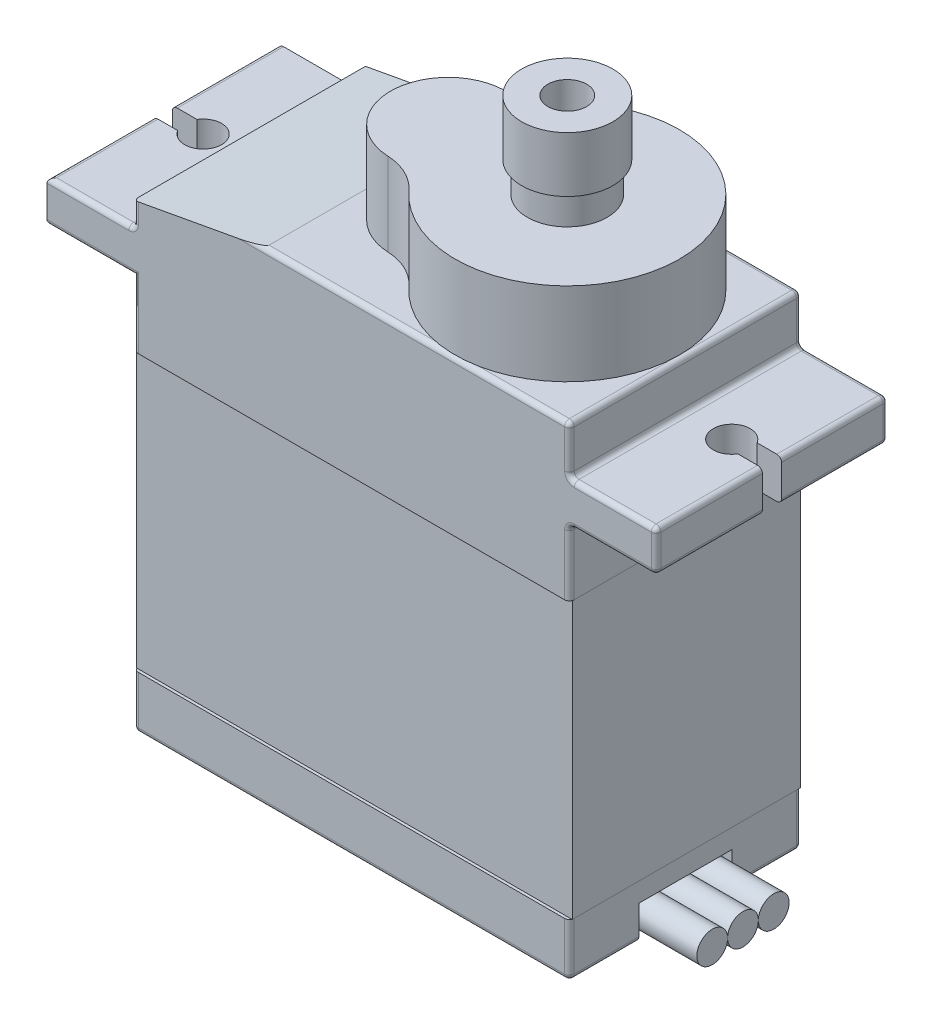
SolidWorks part; units mm, degrees
note: '?' marks a value the reader was unsure of.
ref_plane "Alzado" through (0, 0, 0) normal (0, 0, 1) x (1, 0, 0)
ref_plane "Planta" through (0, 0, 0) normal (0, 1, 0) x (1, 0, 0)
ref_plane "Vista lateral" through (0, 0, 0) normal (1, 0, 0) x (0, 0, -1)
sketch "Croquis1" plane through (0, 0, 0) normal (0, 1, 0) x (1, 0, 0)
  line L1 (-11.335, 6.03) -> (11.335, 6.03)
  line L2 (-11.335, 6.03) -> (-11.335, -6.03)
  line L3 (-11.335, -6.03) -> (11.335, -6.03)
  line L4 (11.335, 6.03) -> (11.335, -6.03)
  line L5 (-11.335, 6.03) -> (11.335, -6.03) construction
  line L6 (-11.335, -6.03) -> (11.335, 6.03) construction
  point P0 (0, 0)
  dimension "D1" = 22.67
  dimension "D2" = 12.06
extrude "Saliente-Extruir1" add sketch "Croquis1" along normal blind 25.15
sketch "Croquis2" plane through (11.335, 0, 0) normal (1, 0, 0) x (0, 0, -1)
  line L0 (-6.03, 0) -> (-6.03, 20.53) construction
  line L1 (-6.03, 25.15) -> (-6.03, 0) construction
  line L2 (-6.03, 20.53) -> (6.03, 20.53)
  line L3 (6.03, 25.15) -> (6.03, 0) construction
  line L4 (-6.03, 22.66) -> (6.03, 22.66)
  line L5 (-6.03, 22.66) -> (-6.03, 20.53)
  line L6 (6.03, 22.66) -> (6.03, 20.53)
  dimension "D1" = 20.53
  dimension "D2" = 2.13
extrude "Saliente-Extruir2" add sketch "Croquis2" along normal blind 4.51
sketch "Croquis5" plane through (-11.335, 0, 0) normal (-1, 0, 0) x (0, 0, 1)
  line L1 (6.03, 25.15) -> (6.03, 0) construction
  line L2 (-6.03, 22.66) -> (6.03, 22.66)
  line L3 (-6.03, 22.66) -> (-6.03, 20.53)
  line L4 (-6.03, 20.53) -> (6.03, 20.53)
  line L5 (6.03, 22.66) -> (6.03, 20.53)
  line L8 (-6.03, 0) -> (6.03, 0) construction
  dimension "D1" = 20.53
extrude "Saliente-Extruir3" add sketch "Croquis5" along normal blind 4.51
fillet "Redondeo1" radius 0.25 30 edges at (11.335, 0, 0) (0, 0, -6.03) (0, 0, 6.03) (-11.335, 0, 0) (0, 25.15, -6.03) (0, 25.15, 6.03) (-11.335, 25.15, 0) (11.335, 25.15, 0) (15.845, 21.595, -6.03) (15.845, 21.595, 6.03) (15.845, 20.53, 0) (15.845, 22.66, 0) (-15.845, 20.53, 0) (-15.845, 22.66, 0)
sketch "Croquis6" plane through (0, 22.66, 0) normal (0, 1, 0) x (1, 0, 0)
  line L0 (-15.595, 6.03) -> (-11.585, -5.78) construction
  line L1 (-11.585, -5.78) -> (-11.585, 6.03) construction
  line L2 (-11.585, 6.03) -> (-15.595, -5.78) construction
  line L3 (0, 0) -> (0, 5.78) construction
  line L4 (11.085, 5.78) -> (-11.085, 5.78) construction
  line L5 (0, 5.78) -> (0, -5.78) construction
  line L6 (-11.085, -5.78) -> (11.085, -5.78) construction
  line L7 (-22.4686, 0) -> (24.1195, 0) construction
  line L9 (-14.5695, 0.5) -> (-16.5695, 0.5)
  line L10 (-14.5695, -0.5) -> (-16.5695, -0.5)
  line L11 (-16.5695, -0.5) -> (-16.5695, 0.5)
  line L12 (14.5695, 0.5) -> (16.5695, 0.5)
  line L13 (16.5695, -0.5) -> (16.5695, 0.5)
  line L14 (14.5695, -0.5) -> (16.5695, -0.5)
  arc A0 (-14.5695, -0.5) -> (-14.5695, 0.5) centre (-13.75, 0) ccw
  arc A1 (14.5695, -0.5) -> (14.5695, 0.5) centre (13.75, 0) cw
  point P20 (-16.5695, 0)
  dimension "D1" = 1.92
  dimension "D2" = 27.5
  dimension "D3" = 1
  dimension "D4" = 2
extrude "Cortar-Extruir12" cut sketch "Croquis6" against normal blind 4.51
sketch "Croquis8" plane through (0, 25.15, 0) normal (0, 1, 0) x (1, 0, 0)
  line L0 (11.085, 0) -> (-11.085, 0) construction
  line L1 (0, 15.0354) -> (0, -9.7672) construction
  line L2 (13.75, 2.8581) -> (13.75, -7.7295) construction
  line L3 (11.085, -5.78) -> (11.085, 5.78) construction
  line L4 (-11.085, 5.78) -> (-11.085, -5.78) construction
  line L5 (11.085, 5.78) -> (-11.085, 5.78) construction
  line L6 (11.085, 0) -> (-1, 0) construction
  arc A0 (0.9293, -3.9766) -> (0.999, 3.9421) centre (5.25, -0.055) ccw
  arc A1 (-1.0933, 2.9985) -> (-1.146, -2.9964) centre (-1, 0) ccw
  arc A2 (-1.146, -2.9964) -> (0.9293, -3.9766) centre (-1.2921, -5.9929) cw
  arc A3 (-1.0933, 2.9985) -> (0.999, 3.9421) centre (-1.1866, 5.9971) ccw
  dimension "D1" = 3
  dimension "D3" = 1
  dimension "D4" = 3
  dimension "D2" = 8.5
extrude "Saliente-Extruir4" add sketch "Croquis8" along normal blind 4.32 separate body
sketch "Croquis9" plane through (0, 29.47, 0) normal (0, 1, 0) x (1, 0, 0)
  line L0 (5.25, 5.78) -> (5.25, -0.055) construction
  line L1 (11.085, 5.78) -> (-11.085, 5.78) construction
  arc A0 (0.9293, -3.9766) -> (0.999, 3.9421) centre (5.25, -0.055) ccw construction
  circle A1 centre (5.25, -0.055) radius 2.075
  dimension "D1" = 4.15
extrude "Saliente-Extruir5" add sketch "Croquis9" along normal blind 1.58 separate body
sketch "Croquis10" plane through (0, 31.05, 0) normal (0, 1, 0) x (1, 0, 0)
  circle A0 centre (5.25, -0.055) radius 2.385
extrude "Saliente-Extruir6" add sketch "Croquis10" along normal blind 2.88 separate body
sketch "Croquis11" plane through (0, 33.93, 0) normal (0, 1, 0) x (1, 0, 0)
  circle A0 centre (5.25, -0.055) radius 1.01
  dimension "D1" = 2.02
extrude "Cortar-Extruir13" cut sketch "Croquis11" against normal blind 3.88
sketch "Croquis12" plane through (0, 33.93, 0) normal (0, 1, 0) x (1, 0, 0)
  circle A2 centre (5.25, -0.055) radius 2.375
  circle A3 centre (5.25, -0.055) radius 2.385
  dimension "D4" = 4.75
extrude "Cortar-Extruir14" cut sketch "Croquis12" along a picked direction on the side against the normal blind 2.88
sketch "Croquis13" plane through (0, 0, 6.03) normal (0, 0, 1) x (1, 0, 0)
  line L0 (-4.5405, 25.15) -> (-11.335, 23.905) construction
  line L1 (-11.085, 25.15) -> (11.085, 25.15) construction
  line L2 (-11.335, 22.91) -> (-11.335, 24.9) construction
  line L3 (-4.5405, 25.15) -> (-11.335, 23.905)
  line L4 (-11.335, 23.905) -> (-11.335, 25.15)
  line L5 (-11.335, 25.15) -> (-4.5405, 25.15)
extrude "Cortar-Extruir15" cut sketch "Croquis13" against normal blind 16.88
sketch "Croquis14" plane through (0, 0, 6.03) normal (0, 0, 1) x (1, 0, 0)
  line L0 (-11.085, 17.1) -> (11.085, 17.1)
  line L1 (-11.085, 20.78) -> (-11.085, 0.25) construction
  line L2 (11.085, 0.25) -> (11.085, 20.28) construction
  line L3 (11.085, 24.9) -> (-5.9049, 24.9) construction
  line L4 (-11.085, 2.77) -> (11.085, 2.77)
  line L5 (-11.085, 0.25) -> (11.085, 0.25) construction
  line L6 (11.085, 17.1) -> (11.085, 2.77)
  line L7 (-11.085, 17.1) -> (-11.085, 2.77)
  dimension "D1" = 7.8
  dimension "D2" = 2.52
extrude "Cortar-Extruir16" cut sketch "Croquis14" against normal blind 16.88
sketch "Croquis16" plane through (-11.335, 0, 0) normal (-1, 0, 0) x (0, 0, 1)
  line L0 (5.78, 17.1096) -> (-5.78, 17.1096)
  line L3 (5.78, 0.25) -> (5.78, 20.53) construction
  line L4 (-5.78, 20.53) -> (-5.78, 0.25) construction
  line L5 (-5.78, 2.7548) -> (5.78, 2.7548)
  line L6 (5.78, 17.1096) -> (5.78, 2.7548)
  line L7 (-5.78, 2.7548) -> (-5.78, 17.1096)
extrude "Cortar-Extruir17" cut sketch "Croquis16" against normal blind 27.88
sketch "Croquis17" plane through (0, 0, 0) normal (0, 0, 1) x (1, 0, 0)
  line L0 (-11.335, 17.1096) -> (11.335, 17.1096)
  line L1 (11.335, 17.1096) -> (11.335, 2.7548)
  line L2 (11.335, 2.7548) -> (-11.335, 2.7548)
  line L3 (-11.335, 2.7548) -> (-11.335, 17.1096)
extrude "Cortar-Extruir18" cut sketch "Croquis17" against normal blind 27.88 and the other way blind 27.88
sketch "Croquis18" plane through (0, 0, 0) normal (0, 0, 1) x (1, 0, 0)
  line L0 (-11.335, 17.1096) -> (-11.335, 2.7548)
  line L1 (-11.335, 2.7548) -> (11.335, 2.7548)
  line L2 (11.335, 2.7548) -> (11.335, 17.1096)
  line L3 (11.335, 17.1096) -> (-11.335, 17.1096)
extrude "Saliente-Extruir7" add sketch "Croquis18" along normal blind 5.88 and the other way blind 6 separate body
sketch "Croquis19" plane through (11.335, 0, 0) normal (1, 0, 0) x (0, 0, -1)
  line L0 (5.78, 1.5024) -> (2.42, 1.5024) construction
  line L1 (5.78, 0.25) -> (5.78, 2.7548) construction
  line L2 (0, 2.7548) -> (0, 1.7548) construction
  line L4 (-5.78, 1.5024) -> (-2.42, 1.5024) construction
  line L5 (6, 2.7548) -> (-5.88, 2.7548) construction
  line L6 (-2.42, 1.7548) -> (2.42, 1.7548)
  line L7 (2.42, 1.7548) -> (2.42, 0)
  line L8 (5.78, 0) -> (-5.78, 0) construction
  line L9 (2.42, 0) -> (-2.42, 0)
  line L10 (-2.42, 0) -> (-2.42, 1.7548)
  dimension "D1" = 3.36
  dimension "D2" = 1
extrude "Cortar-Extruir19" cut sketch "Croquis19" against normal blind 1.6
sketch "Croquis20" plane through (9.735, 0, 0) normal (1, 0, 0) x (0, 0, -1)
  line L0 (0, 1.7548) -> (0, 0) construction
  line L1 (2.42, 1.7548) -> (-2.42, 1.7548) construction
  line L2 (0, 0.8774) -> (2.42, 0.8774) construction
  line L3 (2.42, 0) -> (2.42, 1.7548) construction
  line L4 (0, 0.8774) -> (-2.42, 0.8774) construction
  line L5 (-2.42, 1.7548) -> (-2.42, 0) construction
  circle A0 centre (0, 0.8774) radius 0.8
  circle A1 centre (-1.6, 0.8774) radius 0.8
  circle A2 centre (1.6, 0.8774) radius 0.8
  dimension "D1" = 1.6
  dimension "D2" = 1.6
  dimension "D3" = 1.6
extrude "Saliente-Extruir8" add sketch "Croquis20" along normal blind 4.6 separate body contours A1 | A0 | A2
ref_axis "Axis1" through (5.25, 31.05, 0.055) along (0, 1, 0)?
ref_plane "Plane1" through (5.25, 0, 0) normal (1, 0, 0) x (0, 0, -1)
